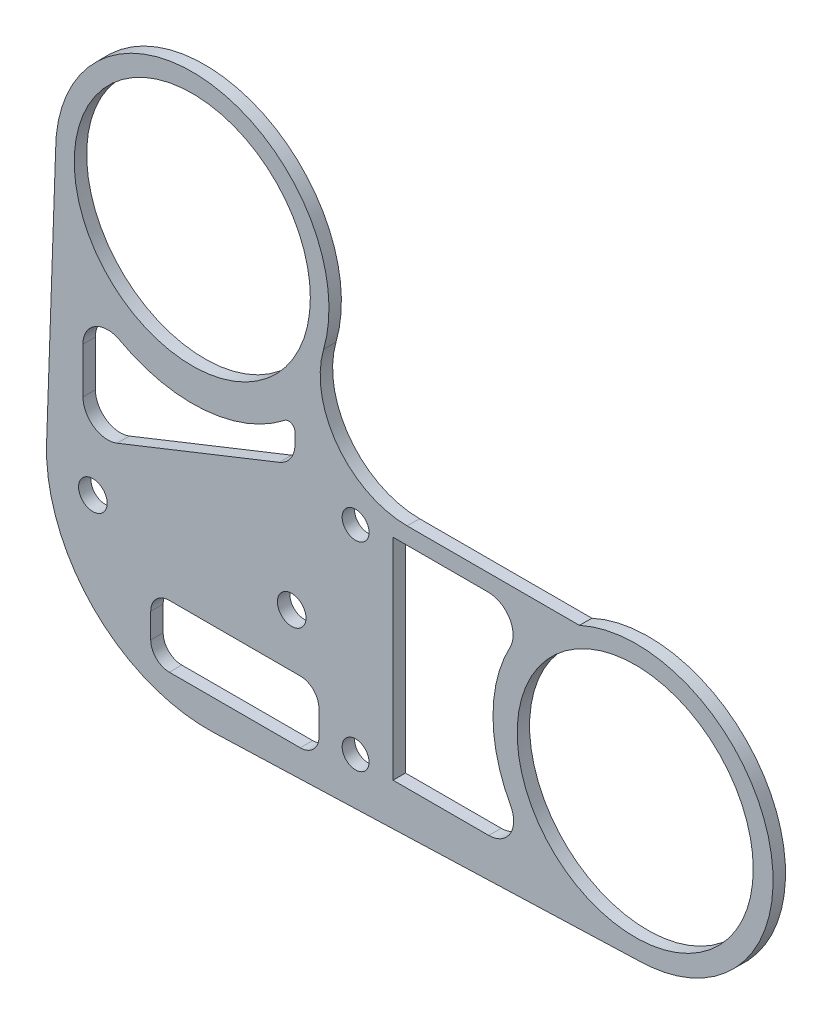
SolidWorks part; units mm, degrees
material "1.5918 (17CrNi6-6)"
ref_plane "前视基准面" through (0, 0, 0) normal (0, 0, 1) x (1, 0, 0)
ref_plane "上视基准面" through (0, 0, 0) normal (0, 1, 0) x (1, 0, 0)
ref_plane "右视基准面" through (0, 0, 0) normal (1, 0, 0) x (0, 0, -1)
sketch "草图3" plane through (0, 0, 0) normal (0, 0, 1) x (1, 0, 0)
  line L0 (-11, 0) -> (-11, -33)
  line L1 (35.74, -33) -> (-11, -33)
  line L2 (31.1574, -12) -> (9, -12)
  line L3 (9, -12) -> (9, -6.3246)
  arc A0 (9, -6.3246) -> (-11, 0) centre (0, 0) ccw
  arc A1 (35.74, -33) -> (31.1574, -12) centre (35.74, -22) ccw
  circle A2 centre (0, 0) radius 9.5
  circle A3 centre (35.74, -22) radius 9.5
  dimension "D1" = 35.74
  dimension "D2" = 22
  dimension "D4" = 19
  dimension "D3" = 22
  dimension "D5" = 10
  dimension "D6" = 9
extrude "凸台-拉伸1" add sketch "草图3" along normal blind 1
sketch "草图4" plane through (0, 0, 1) normal (0, 0, 1) x (1, 0, 0)
  line L0 (35.74, -33) -> (-12.2109, -34.6745)
  line L1 (-12.2109, -34.6745) -> (-11, 0)
  line L2 (-11, -33) -> (35.74, -33) construction
  line L3 (-11, 0) -> (-11, -33) construction
  line L8 (-11, 0) -> (-11, -33)
  line L9 (-11, -33) -> (35.74, -33)
  line L10 (31.1574, -12) -> (9, -12)
  line L11 (9, -12) -> (9, -6.3246)
  line L14 (31.1574, -12) -> (9, -12)
  line L15 (9, -12) -> (9, -6.3246)
  arc A2 (9, -6.3246) -> (-11, 0) centre (0, 0) ccw
  arc A3 (35.74, -33) -> (31.1574, -12) centre (35.74, -22) ccw
  arc A4 (9, -6.3246) -> (-11, 0) centre (0, 0) ccw
  arc A5 (35.74, -33) -> (31.1574, -12) centre (35.74, -22) ccw
  dimension "D1" = 2
  dimension "D2" = 2
  dimension "D3" = 0
extrude "凸台-拉伸2" add sketch "草图4" against normal blind 1
fillet "圆角2" radius 13 1 edges at (-12.2109, -34.6745, 0.5)
sketch "草图5" plane through (0, 0, 1) normal (0, 0, 1) x (1, 0, 0)
  line L0 (0, 0) -> (0, -6.5656) construction
  circle A0 centre (-8, -22.5) radius 1.15
  circle A1 centre (8, -22.5) radius 1.15
  dimension "D3" = 2.3
  dimension "D4" = 8
  dimension "D1" = 16
  dimension "D2" = 22.5
extrude "切除-拉伸1" cut sketch "草图5" against normal through all
sketch "草图6" plane through (0, 0, 1) normal (0, 0, 1) x (1, 0, 0)
  circle A0 centre (0, 0) radius 9.5
  circle A2 centre (35.6428, -22) radius 9.5
  dimension "D1" = 19
extrude "切除-拉伸2" cut sketch "草图6" against normal through all
fillet "圆角3" radius 8 1 edges at (9, -12, 0.5)
fillet "圆角4" radius 7 1 edges at (9, -6.3246, 0.5)
sketch "草图7" plane through (0, 0, 1) normal (0, 0, 1) x (1, 0, 0)
  line L0 (45.1428, -22) -> (2.3972, -22) construction
  circle A0 centre (35.6428, -22) radius 9.5 construction
  circle A1 centre (13.1428, -14) radius 1.0833
  circle A2 centre (13.1428, -30) radius 1.0833
  dimension "D1" = 22.5
  dimension "D2" = 8
extrude "切除-拉伸4" cut sketch "草图7" against normal blind 10
sketch "草图8" plane through (0, 0, 1) normal (0, 0, 1) x (1, 0, 0)
  line L0 (16.1572, -30.2911) -> (16.1572, -13.3557)
  line L1 (-1.8442, -26.7629) -> (8.6913, -26.7629)
  line L2 (-3.3442, -28.2629) -> (-3.3442, -30.2665)
  line L3 (-1.8442, -31.7665) -> (8.6913, -31.7665)
  line L4 (10.1913, -28.2629) -> (10.1913, -30.2665)
  line L5 (16.1572, -13.3557) -> (23.8187, -13.3557)
  line L6 (16.1572, -30.2911) -> (23.8592, -30.2911)
  line L7 (-8.7969, -16.0529) -> (-8.7969, -12.3803)
  line L9 (-6.0577, -17.9113) -> (6.9986, -12.7179)
  line L10 (8.2594, -10.8596) -> (8.2594, -9.957)
  arc A1 (25.5804, -16.3025) -> (25.615, -27.3333) centre (35.7832, -21.786) ccw
  arc A3 (-5.8344, -10.6271) -> (7.452, -9.5626) centre (0, 0) ccw
  arc A5 (-8.7969, -12.3803) -> (-5.8344, -10.6271) centre (-6.7969, -12.3803) cw
  arc A6 (8.2594, -10.8596) -> (6.9986, -12.7179) centre (6.2594, -10.8596) cw
  arc A7 (-8.7969, -16.0529) -> (-6.0577, -17.9113) centre (-6.7969, -16.0529) ccw
  arc A8 (8.2594, -9.957) -> (7.452, -9.5626) centre (7.7594, -9.957) ccw
  arc A9 (25.615, -27.3333) -> (23.8592, -30.2911) centre (23.8592, -28.2911) cw
  arc A10 (23.8187, -13.3557) -> (25.5804, -16.3025) centre (23.8187, -15.3557) cw
  arc A11 (-3.3442, -30.2665) -> (-1.8442, -31.7665) centre (-1.8442, -30.2665) ccw
  arc A12 (-3.3442, -28.2629) -> (-1.8442, -26.7629) centre (-1.8442, -28.2629) cw
  arc A13 (10.1913, -30.2665) -> (8.6913, -31.7665) centre (8.6913, -30.2665) cw
  arc A14 (10.1913, -28.2629) -> (8.6913, -26.7629) centre (8.6913, -28.2629) ccw
  point P21 (8.2594, -12.2164)
  dimension "D1" = 2
  dimension "D2" = 2
  dimension "D3" = 0.5
  dimension "D4" = 2
  dimension "D5" = 1.5
extrude "切除-拉伸5" cut sketch "草图8" against normal blind 10
